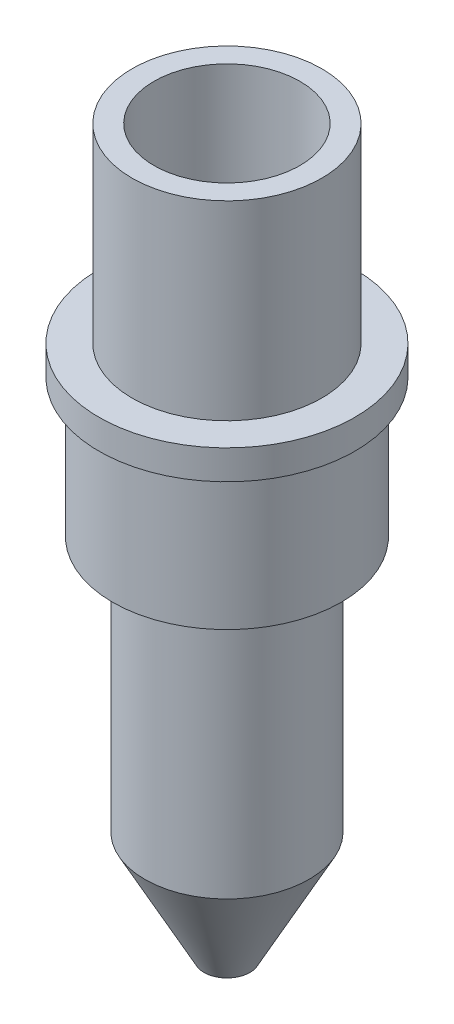
SolidWorks part; units mm, degrees
ref_plane "Front Plane" through (0, 0, 0) normal (0, 0, 1) x (1, 0, 0)
ref_plane "Top Plane" through (0, 0, 0) normal (0, 1, 0) x (1, 0, 0)
ref_plane "Right Plane" through (0, 0, 0) normal (1, 0, 0) x (0, 0, -1)
sketch "Sketch1" plane through (0, 0, 0) normal (0, 1, 0) x (1, 0, 0)
  circle A0 centre (0, 0) radius 10.33
  circle A1 centre (0, 0) radius 7.95
  dimension "D1" = 20.66
  dimension "D2" = 15.9
extrude "Boss-Extrude1" add sketch "Sketch1" along normal blind 20.74
sketch "Sketch2" plane through (0, 0, 0) normal (0, -1, 0) x (1, 0, 0)
  circle A0 centre (0, 0) radius 13.94
  dimension "D1" = 27.88
extrude "Boss-Extrude2" add sketch "Sketch2" along normal blind 3.2
sketch "Sketch3" plane through (0, -3.2, 0) normal (0, -1, 0) x (-1, 0, 0)
  circle A0 centre (0, 0) radius 12.44
  dimension "D1" = 24.88
extrude "Boss-Extrude3" add sketch "Sketch3" along normal blind 15
sketch "Sketch4" plane through (0, -18.2, 0) normal (0, -1, 0) x (-1, 0, 0)
  circle A0 centre (0, 0) radius 8.94
  dimension "D1" = 17.88
extrude "Boss-Extrude4" add sketch "Sketch4" along normal blind 39.88
sketch "Sketch5" plane through (0, 0, 0) normal (1, 0, 0) x (0, 0, -1)
  line L0 (8.94, -46.08) -> (2.5, -58.08)
  line L1 (8.94, -58.08) -> (8.94, -18.2) construction
  line L2 (-8.94, -58.08) -> (8.94, -58.08) construction
  line L3 (2.5, -58.08) -> (8.94, -58.08)
  line L4 (8.94, -58.08) -> (8.94, -46.08)
  line L5 (0, -58.08) -> (0, -18.2) construction
  line L6 (-8.94, -18.2) -> (8.94, -18.2) construction
  dimension "D1" = 12
  dimension "D2" = 2.5
revolve "Cut-Revolve1" cut sketch "Sketch5" angle 360 about L5
sketch "Sketch6" plane through (0, -58.08, 0) normal (0, -1, 0) x (1, 0, 0)
  circle A0 centre (0, 0) radius 2.45
  dimension "D1" = 4.9
extrude "Cut-Extrude1" cut sketch "Sketch6" against normal through all
sketch "Sketch7" plane through (0, 0, 0) normal (0, 1, 0) x (1, 0, 0)
  circle A0 centre (0, 0) radius 5.5
  dimension "D1" = 11
extrude "Cut-Extrude2" cut sketch "Sketch7" against normal blind 46
